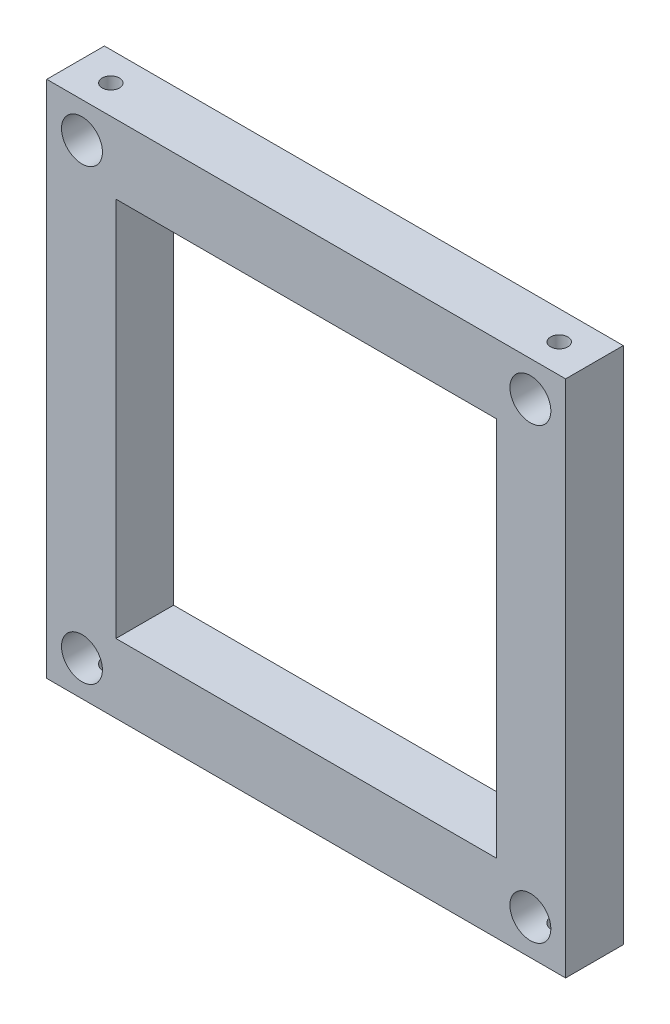
SolidWorks part; units mm, degrees
ref_plane "Front Plane" through (0, 0, 0) normal (0, 0, 1) x (1, 0, 0)
ref_plane "Top Plane" through (0, 0, 0) normal (0, 1, 0) x (1, 0, 0)
ref_plane "Right Plane" through (0, 0, 0) normal (1, 0, 0) x (0, 0, -1)
sketch "Sketch1" plane through (0, 0, 0) normal (0, 0, 1) x (1, 0, 0)
  line L0 (0, 45) -> (0, 0) construction
  line L1 (45, 45) -> (-45, 45)
  line L2 (45, 45) -> (45, -45)
  line L3 (45, -45) -> (-45, -45)
  line L4 (-45, 45) -> (-45, -45)
  line L5 (0, 0) -> (45, 0) construction
  line L7 (33, -33) -> (-33, -33)
  line L8 (33, -33) -> (33, 33)
  line L9 (33, 33) -> (-33, 33)
  line L10 (-33, -33) -> (-33, 33)
  line L13 (-38.89, -38.8883) -> (38.89, -38.8883) construction
  line L14 (-38.89, -38.8883) -> (-38.89, 38.8917) construction
  line L15 (-38.89, 38.8917) -> (38.89, 38.8917) construction
  line L16 (38.89, -38.8883) -> (38.89, 38.8917) construction
  circle A0 centre (-38.89, 38.8917) radius 3.55
  circle A1 centre (38.89, 38.8917) radius 3.55
  circle A2 centre (38.89, -38.8917) radius 3.55
  circle A3 centre (-38.89, -38.8917) radius 3.55
  point P0 (0, 0)
  point P6 (0, 0)
  point P11 (45, 0)
  point P12 (0, 0)
  point P28 (-36.42, -36.3419)
  dimension "D7" = 7.1
  dimension "D8" = 55
  dimension "D1" = 90
  dimension "D2" = 90
  dimension "D3" = 12
  dimension "D4" = 12
  dimension "D5" = 77.78
  dimension "D6" = 77.78
  dimension "D9" = 33
  dimension "D10" = 5.8917
extrude "Boss-Extrude1" add sketch "Sketch1" along normal blind 10
sketch "Sketch2" plane through (0, -45, 0) normal (0, -1, 0) x (1, 0, 0)
  line L0 (-45, 5) -> (45, 5) construction
  line L1 (-45, 10) -> (-45, 0) construction
  line L2 (45, 10) -> (45, 0) construction
  line L3 (0, 0) -> (0, 10) construction
  line L4 (-45, 10) -> (45, 10) construction
  circle A0 centre (-38.89, 5) radius 1.5
  circle A1 centre (38.89, 5) radius 1.5
  dimension "D1" = 77.78
  dimension "D2" = 3
extrude "Cut-Extrude1" cut sketch "Sketch2" against normal up to next
mirror "Mirror1" about plane through (0, 0, 0) normal (0, 1, 0) of "Cut-Extrude1"
